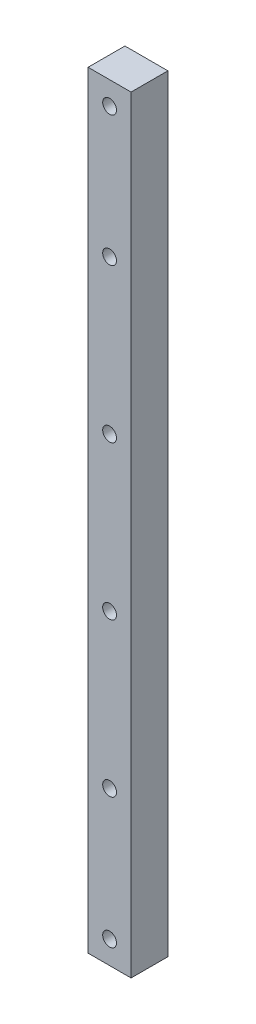
SolidWorks part; units mm, degrees
ref_plane "Front Plane" through (0, 0, 0) normal (0, 0, 1) x (1, 0, 0)
ref_plane "Top Plane" through (0, 0, 0) normal (0, 1, 0) x (1, 0, 0)
ref_plane "Right Plane" through (0, 0, 0) normal (1, 0, 0) x (0, 0, -1)
sketch "Sketch1" plane through (0, 0, 0) normal (0, 1, 0) x (1, 0, 0)
  line L1 (-7, -6) -> (7, -6)
  line L2 (-7, -6) -> (-7, 6)
  line L3 (-7, 6) -> (7, 6)
  line L4 (7, -6) -> (7, 6)
  line L5 (-7, -6) -> (7, 6) construction
  line L6 (-7, 6) -> (7, -6) construction
  point P0 (0, 0)
  dimension "D1" = 12
  dimension "D2" = 14
extrude "Boss-Extrude1" add sketch "Sketch1" along normal blind 250
sketch "Sketch2" plane through (0, 0, 0) normal (0, 0, 1) x (1, 0, 0)
  line L0 (0, 0) -> (0, 46.8982) construction
  circle A0 centre (0, 7.5) radius 2.25
  circle A1 centre (0, 242.5) radius 2.25
  dimension "D1" = 4.5
  dimension "D3" = 4.5
  dimension "D2" = 7.5
  dimension "D4" = 235
extrude "Cut-Extrude1" cut sketch "Sketch2" against normal mid plane 12
sketch "Sketch3" plane through (0, 0, -6) normal (0, 0, -1) x (-1, 0, 0)
  line L0 (0, 250) -> (0, 0) construction
  line L1 (-7, 250) -> (7, 250) construction
  line L2 (-7, 0) -> (7, 0) construction
  circle A0 centre (0, 200) radius 2.25
  circle A1 centre (0, 150) radius 2.25
  circle A2 centre (0, 100) radius 2.25
  circle A3 centre (0, 50) radius 2.25
  dimension "D1" = 4.5
  dimension "D2" = 50
  dimension "D3" = 4
extrude "Cut-Extrude2" cut sketch "Sketch3" against normal up to next
